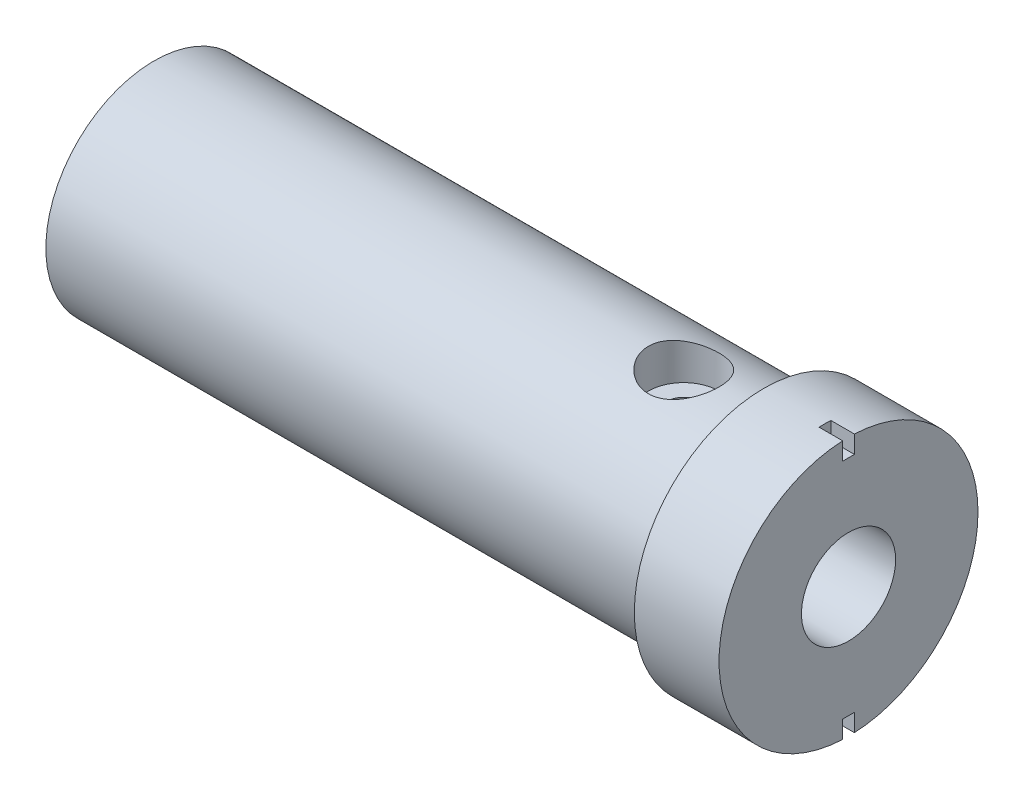
SolidWorks part; units mm, degrees
material "PA Type 6"
ref_plane "Front Plane" through (0, 0, 0) normal (0, 0, 1) x (1, 0, 0)
ref_plane "Top Plane" through (0, 0, 0) normal (0, 1, 0) x (1, 0, 0)
ref_plane "Right Plane" through (0, 0, 0) normal (1, 0, 0) x (0, 0, -1)
sketch "Sketch1" plane through (0, 0, 0) normal (0, 1, 0) x (1, 0, 0)
  line L0 (0, 0) -> (-90.15, 0) construction
  line L1 (0, 0) -> (0, 11)
  line L2 (0, 11) -> (-7.2, 11)
  line L3 (-7.2, 11) -> (-7.2, 9.2)
  line L4 (-7.2, 9.2) -> (-59, 9.2)
  line L5 (-59, 9.2) -> (-59, 0)
  line L6 (0, 0) -> (-59, 0)
  dimension "D1" = 7.2
  dimension "D2" = 59
  dimension "D3" = 11
  dimension "D4" = 9.2
revolve "Revolve1" add sketch "Sketch1" angle 360 about L0
sketch "Sketch2" plane through (0, 0, 0) normal (1, 0, 0) x (0, 0, -1)
  line L0 (-2.5278, 3.1) -> (2.5278, 3.1)
  line L1 (0.5, 10.9886) -> (0.5, 9.4886)
  line L2 (0.5, 9.4886) -> (-0.5, 9.4886)
  line L3 (-0.5, 9.4886) -> (-0.5, 10.9886)
  line L4 (0, 0) -> (4, 0) construction
  line L5 (-0.5, -9.4886) -> (-0.5, -10.9886)
  line L6 (0.5, -9.4886) -> (-0.5, -9.4886)
  line L7 (0.5, -10.9886) -> (0.5, -9.4886)
  circle A0 centre (0, 0) radius 4
  circle A1 centre (0, 0) radius 11 construction
  circle A2 centre (0, 0) radius 11
  circle M3 centre (0, 0) radius 11
  dimension "D1" = 8
  dimension "D2" = 3.1
  dimension "D3" = 0.5
  dimension "D4" = 1
  dimension "D5" = 1.5
extrude "Cut-Extrude1" cut sketch "Sketch2" against normal blind 21 contours L0 A0 region at (0, -0.2284, 0)
extrude "Cut-Extrude2" cut sketch "Sketch2<4>" against normal blind 2 contours L0 A0 region at (0, 3.4637, 0)
sketch "Sketch2<4>" plane through (0, 0, 0) normal (1, 0, 0) x (0, 0, -1) same geometry as "Sketch2"
sketch "Sketch3" plane through (0, 3.1, 0) normal (0, -1, 0) x (1, 0, 0)
  line L0 (0, 0) -> (-14, 0) construction
  circle A1 centre (-14, 0) radius 1.475
  circle A2 centre (-14, 0) radius 3
  dimension "D2" = 2.95
  dimension "D3" = 6
  dimension "D1" = 14
extrude "Cut-Extrude3" cut sketch "Sketch3" against normal through all contours A1 region at (-14, 3.1, 0)
sketch "Sketch4" plane through (-59, 0, 0) normal (-1, 0, 0) x (0, 0, 1)
  line L0 (3.0215, 3.1) -> (3.0215, 8.6897) construction
  line L1 (-3, 3.1) -> (3, 3.1) construction
  line L2 (3.0215, 8.6897) -> (-3, 8.6897) construction
  line L3 (-3, 8.6897) -> (-3, 3.1) construction
  circle A1 centre (0, 0) radius 9.2 construction
  dimension "D1" = 5.5897
extrude "Cut-Extrude4" cut sketch "Sketch3<4>" against normal through all from offset 2.8 offset against normal yes
sketch "Sketch3<4>" plane through (0, 3.1, 0) normal (0, -1, 0) x (1, 0, 0) same geometry as "Sketch3"
extrude "Cut-Extrude5" cut sketch "Sketch2<6>" against normal blind 2 contours L3 L2 L1 M3 | L7 L6 L5 M3 region at (0, 10.2424, 0) region at (0, -10.2424, 0)
sketch "Sketch2<6>" plane through (0, 0, 0) normal (1, 0, 0) x (0, 0, -1) same geometry as "Sketch2"
